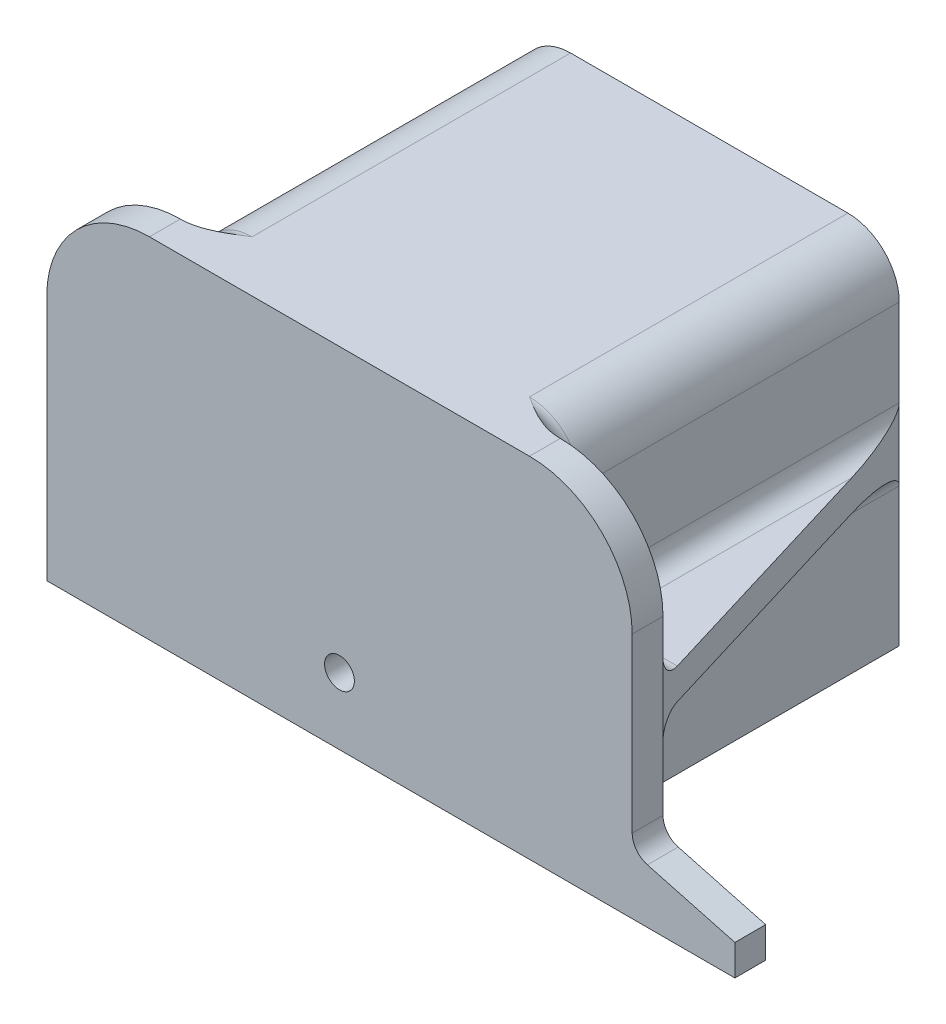
SolidWorks part; units mm, degrees
material "ABS"
ref_plane "Front Plane" through (0, 0, 0) normal (0, 0, 1) x (1, 0, 0)
ref_plane "Top Plane" through (0, 0, 0) normal (0, 1, 0) x (1, 0, 0)
ref_plane "Right Plane" through (0, 0, 0) normal (1, 0, 0) x (0, 0, -1)
sketch "Sketch1" plane through (0, 0, 0) normal (0, 1, 0) x (1, 0, 0)
  line L0 (0, 0) -> (0, -6) construction
  line L1 (15.5, 0) -> (-15.5, 0)
  line L2 (-15.5, 0) -> (-15.5, 30)
  line L3 (-15.5, 30) -> (-18.5, 30)
  line L4 (-28.5, -6) -> (-28.5, -3)
  line L5 (-28.5, -6) -> (28.5, -6)
  line L7 (-18.5, -3) -> (-18.5, 30)
  line L8 (-28.5, -3) -> (-18.5, -3)
  line L9 (28.5, -3) -> (18.5, -3)
  line L10 (18.5, -3) -> (18.5, 30)
  line L12 (28.5, -6) -> (28.5, -3)
  line L13 (15.5, 30) -> (18.5, 30)
  line L14 (15.5, 0) -> (15.5, 30)
  dimension "D1" = 15.5
  dimension "D2" = 30
  dimension "D3" = 6
  dimension "D4" = 3
  dimension "D5" = 10
  dimension "D6" = 3
extrude "Boss-Extrude1" add sketch "Sketch1" along normal mid plane 34
sketch "Sketch2" plane through (0, 0, 0) normal (0, 1, 0) x (1, 0, 0)
  line L0 (18.5, 30) -> (18.5, -3)
  line L1 (18.5, -3) -> (28.5, -3)
  line L2 (28.5, -3) -> (18.5, 30)
extrude "Boss-Extrude2" add sketch "Sketch2" along normal mid plane 3
mirror "Mirror1" about plane through (0, 0, 0) normal (1, 0, 0) of "Boss-Extrude2"
sketch "Sketch3" plane through (0, 0, 0) normal (0, 0, -1) x (-1, 0, 0)
  line L0 (0, 0) -> (0, -10.5) construction
  line L1 (0, -10.5) -> (0, -17) construction
  line L2 (-15.5, -17) -> (15.5, -17) construction
  circle A0 centre (0, -10.5) radius 1.45
  dimension "D2" = 2.9
  dimension "D1" = 6.5
extrude "Cut-Extrude1" cut sketch "Sketch3" against normal through all
fillet "Fillet1" radius 10 2 edges at (28.5, 17, 4.5) (-28.5, 17, 4.5)
sketch "Sketch4" plane through (0, 0, 0) normal (0, 0, -1) x (-1, 0, 0)
  circle A0 centre (0, -10.5) radius 5
  dimension "10mm" = 10
extrude "Cut-Extrude4" cut sketch "Sketch4" against normal blind 2
fillet "Fillet2" radius 0.5 1 edges at (-5, -10.5, 2)
sketch "Sketch5" plane through (0, 0, 0) normal (0, 0, -1) x (-1, 0, 0)
  line L0 (-15.5, 17) -> (-15.5, -17) construction
  line L3 (15.5, 17) -> (-15.5, 17)
  line L7 (15.5, 17) -> (15.5, 14)
  line L8 (15.5, 14) -> (-15.5, 14)
  line L9 (-15.5, 17) -> (-15.5, 14)
  dimension "D1" = 3
extrude "Boss-Extrude3" add sketch "Sketch5" along normal up to surface (30 mm away) up to face at (-17.5, 0, -30)
sketch "Sketch6" plane through (28.5, 0, 0) normal (1, 0, 0) x (0, 0, -1)
  line L0 (-6, -17) -> (-3, -17)
  line L1 (-3, -17) -> (-3, -14)
  line L2 (-3, -1.5) -> (-3, -17) construction
  line L3 (-3, -14) -> (-6, -14)
  line L4 (-6, 7) -> (-6, -17) construction
  line L5 (-6, -14) -> (-6, -17)
extrude "Boss-Extrude4" add sketch "Sketch6" along normal blind 10
chamfer "Chamfer1" distance 10 angle 15 1 edges at (28.5, -14, 4.5) first distance on face at (33.5, -14, 4.5)
fillet "Fillet3" radius 5 4 edges at (-15.5, 14, -15) (15.5, 14, -15) (-18.5, 17, -13.5) (18.5, 17, -13.5)
fillet "Fillet4" radius 2 15 edges at (-17.0355, 15.5355, 3) (17.0355, 15.5355, 3) (-18.5, -1.5, -13.5) (-23.5, -1.5, 3) (-23.5, 1.5, 3) (-18.5, 1.5, -13.5) (-18.5, 6.75, 3) (-18.5, -9.25, 3) (18.5, 6.75, 3) (18.5, -9.25, 3) (18.5, -1.5, -13.5) (23.5, -1.5, 3) (23.5, 1.5, 3) (18.5, 1.5, -13.5) (28.5, -11.3205, 4.5)
